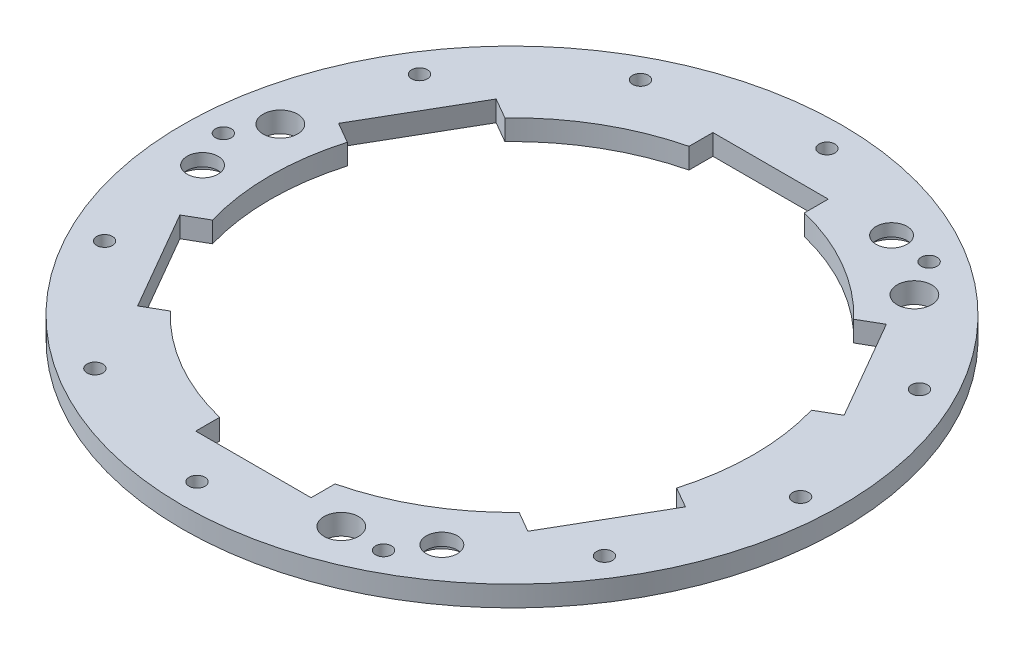
SolidWorks part; units mm, degrees
material "6061 Alloy"
ref_plane "Front Plane" through (0, 0, 0) normal (0, 0, 1) x (1, 0, 0)
ref_plane "Top Plane" through (0, 0, 0) normal (0, 1, 0) x (1, 0, 0)
ref_plane "Right Plane" through (0, 0, 0) normal (1, 0, 0) x (0, 0, -1)
sketch "Sketch1" plane through (0, 0, 0) normal (0, 1, 0) x (1, 0, 0)
  line L0 (-13.335, -54.2656) -> (-13.335, -58.1814)
  line L1 (13.335, -54.2656) -> (13.335, -58.1814)
  line L2 (-13.335, -59.7901) -> (13.335, -59.7901)
  line L3 (13.335, -58.1814) -> (13.335, -59.7901)
  line L4 (-13.335, -58.1814) -> (-13.335, -59.7901)
  line L5 (0, 0) -> (-65.7887, -5.7558) construction
  line L6 (0, 0) -> (-3.0468, -69.7835) construction
  line L7 (0, 0) -> (0, -26.4169) construction
  line L9 (-65.0367, 11.4677) -> (0, 0) construction
  circle A0 centre (0, 0) radius 55.88
  circle A1 centre (0, 0) radius 76.2
  circle A2 centre (0, 0) radius 59.69
  circle A3 centre (-3.0468, -69.7835) radius 1.8288
  circle A4 centre (-65.7887, -5.7558) radius 3.589
  circle A5 centre (-65.0367, 11.4677) radius 3.9903
  point P24 (0, 0)
  point P29 (0, 0)
  dimension "D1" = 111.76
  dimension "D2" = 152.4
  dimension "D8" = 3.6576
  dimension "D11" = 7.178
  dimension "D12" = 7.9807
  dimension "D4" = 13.335
  dimension "D5" = 13.335
  dimension "D7" = 69.85
  dimension "D6" = 5.5245
  dimension "D9" = 66.04
  dimension "D10" = 82.5
  dimension "D15" = 15
  dimension "D13" = 2.5
  dimension "D3" = 3.81
extrude "Boss-Extrude1" add sketch "Sketch1" along normal blind 4.7625 contours L1 A2 L0 A0 | A1 A2 A0 region at (-15.0127, 0, 56.2235) region at (-74.0447, 0, 0)
pattern_circular "CirPattern1" count 6 over 360 about axis through (0, 4.7625, 0) along (0, 1, 0) of face at (-13.335, 2.3813, 57.0278) of face at (13.335, 2.3813, 57.0278) of face at (0, 2.3813, 59.7901)
pattern_circular "CirPattern7" count 12 over 360 about axis through (0, 4.7625, 0) along (0, 1, 0) of face at (-3.0468, 4.7625, 71.6123)
sketch "Sketch4" plane through (0, 0, 0) normal (0, -1, 0) x (1, 0, 0)
  line L0 (0, 0) -> (-65.7887, 5.7558) construction
  line L1 (0, 0) -> (0, -39.7137) construction
  circle A0 centre (-65.7887, 5.7558) radius 5.588
  circle A2 centre (-65.7887, 5.7558) radius 3.589 construction
  circle A3 centre (-65.7887, 5.7558) radius 3.589
  point P12 (0, 0)
  dimension "D2" = 11.176
extrude "Cut-Extrude1" cut sketch "Sketch4" against normal blind 1.905 contours A0 region at (-71.2186, 0, 5.7558)
pattern_circular "CirPattern2" count 3 over 360 about axis through (0, 0, 0) along (0, 1, 0) of face at (-65.7887, 4.7625, 9.3448) of face at (-65.7887, 1.905, 2.1667) of face at (-65.7887, 1.905, 0.1678) of face at (-65.0367, 4.7625, -7.4774)
sketch "Sketch5" plane through (0, 4.7625, 0) normal (0, 1, 0) x (1, 0, 0)
  line L0 (0, 0) -> (-20.0894, -55.1952)
  line L1 (0, 0) -> (0, -18.6852)
  line L2 (-16.5968, -53.0258) -> (-18.2257, -57.5011) construction
  line L3 (-18.2257, -57.5011) -> (-22.9993, -55.7636) construction
  line L4 (-22.9993, -55.7636) -> (-21.3704, -51.2884) construction
  line L5 (-59.7924, -7.9638) -> (-55.1022, -7.1368)
  line L6 (-54.2201, -12.1397) -> (-58.9103, -12.9667)
  line L7 (-58.9103, -12.9667) -> (-59.7924, -7.9638)
  line L8 (-36.7931, 47.7998) -> (-33.7318, 44.1515)
  line L9 (-37.6233, 40.8862) -> (-40.6846, 44.5345)
  line L10 (-40.6846, 44.5345) -> (-36.7931, 47.7998)
  line L11 (22.9993, 55.7636) -> (21.3704, 51.2884)
  line L12 (16.5968, 53.0258) -> (18.2257, 57.5011)
  line L13 (18.2257, 57.5011) -> (22.9993, 55.7636)
  line L14 (59.7924, 7.9638) -> (55.1022, 7.1368)
  line L15 (54.2201, 12.1397) -> (58.9103, 12.9667)
  line L16 (58.9103, 12.9667) -> (59.7924, 7.9638)
  line L17 (36.7931, -47.7998) -> (33.7318, -44.1515)
  line L18 (37.6233, -40.8862) -> (40.6846, -44.5345)
  line L19 (40.6846, -44.5345) -> (36.7931, -47.7998)
  circle A0 centre (0, 0) radius 55.5625
  circle A1 centre (0, 0) radius 58.7375 construction
  circle A2 centre (0, 0) radius 55.5625
  circle A3 centre (0, 0) radius 55.5625
  circle A4 centre (0, 0) radius 55.5625
  circle A5 centre (0, 0) radius 55.5625
  circle A6 centre (0, 0) radius 55.5625
  circle A7 centre (0, 0) radius 76.2
  circle A8 centre (0, 0) radius 63.5
  point P38 (0, 0)
  dimension "D1" = 111.125
  dimension "D3" = 20
  dimension "D4" = 2.54
  dimension "D5" = 4.7625
  dimension "D6" = 2.54
  dimension "D2" = 3.175
  dimension "D8" = 12.7
  dimension "D7" = 6
split line "Split Line1" [suppressed]
equation "\"Middle Coupler Inner Daimeter\"= 3.875in"
equation "\"Middle Coupler  Wall Thickness\"= 0.25in"
equation "\"Middle Coupler Bottom Thickness\"= 0.2in"
equation "\"Bearing Rail Offset\"= 0.45in"
equation "\"3-56 UNF Tap\"= 0.089in"
equation "\"3-56 UNF Clearance\"= 0.104in"
equation "\"Ball Bearing Distance\"= 0.03in"
equation "\"D1@Sketch1\"=\"Middle Coupler Inner Daimeter\"+0.5+0.0125*2in"
equation "\"TCA Outer Diameter\"= 6in"
equation "\"D2@Sketch1\"=\"TCA Outer Diameter\""
equation "\"D4@Sketch1\"=0.50 + (0.05/2)"
equation "\"D5@Sketch1\"=\"D4@Sketch1\""
equation "\"D7@Sketch1\"=(\"D2@Sketch1\"-0.5)/2"
equation "\"D8@Sketch1\"=\"6-32 Clearance\""
equation "\"Interstage Aeroframe Wall Thickness\"= 0.072in"
equation "\"Compression Spring OD\"= 0.42in"
equation "\"10-24 Tap\"= 0.157in"
equation "\"10-24 Clearance\"= 0.196in"
equation "\"D2@Sketch4\"=\"Compression Spring OD\"+0.02"
equation "\"D3@Sketch1\"=0.125in+(0.05/2)"
equation "\"Lower Stage Fuselage Wall Thickness\"= 0.25in"
equation "\"6-32 Tap\"= 0.107in"
equation "\"1/4-20 Tap\"= 0.201in"
equation "\"3-48 Tap\"= 0.079in"
equation "\"12-24 Tap\"= 0.177in"
equation "\"3-48 Clearance\"= 0.104in"
equation "\"6-32 Clearance\"= 0.144"
equation "\"D6@Sketch1\"=3/16 + 0.03"
equation "\"D9@Sketch1\"=(\"D2@Sketch1\"+\"D1@Sketch1\")/4+0.1-.1"
equation "\"D1@Sketch5\"=\"Middle Coupler Inner Daimeter\"+0.5"
equation "\"D5@Sketch5\"=3/16"
equation "\"D6@Sketch5\"=\"D4@Sketch5\""
equation "\"D1@Boss-Extrude1\"=3/16"
